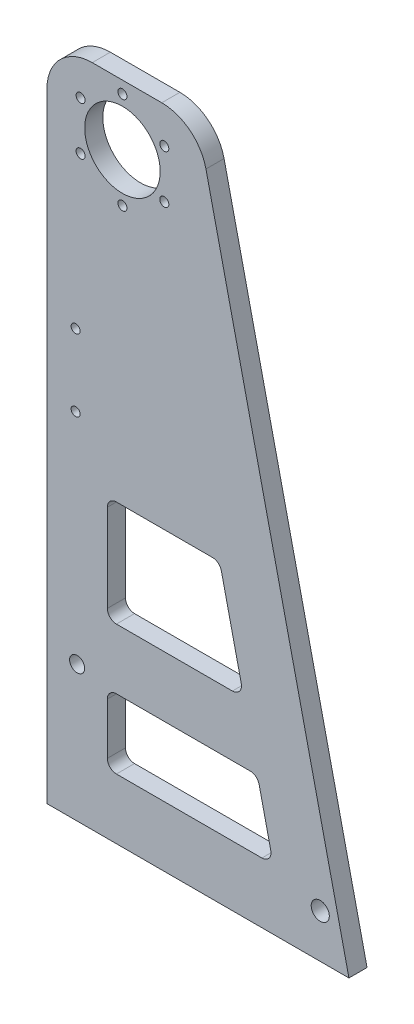
SolidWorks part; units mm, degrees
material "Policarbonato"
ref_plane "Plano frontal" through (0, 0, 0) normal (0, 0, 1) x (1, 0, 0)
ref_plane "Plano superior" through (0, 0, 0) normal (0, 1, 0) x (1, 0, 0)
ref_plane "Plano direito" through (0, 0, 0) normal (1, 0, 0) x (0, 0, -1)
sketch "Esboço1" plane through (0, 0, 0) normal (0, 0, 1) x (1, 0, 0)
  line L0 (0, 0) -> (0, 220)
  line L2 (100, 0) -> (0, 0)
  line L3 (0, 220) -> (50, 220)
  line L4 (50, 220) -> (100, 0)
  line L5 (10, 75.5) -> (10, 15) construction
  line L6 (25, 220) -> (25, 180) construction
  line L7 (10, 15) -> (85.7122, 15) construction
  line L8 (85.7122, 15) -> (71.9622, 75.5) construction
  line L9 (71.9622, 75.5) -> (10, 75.5) construction
  line L10 (20, 95) -> (20, 66)
  line L11 (23, 63) -> (61.4135, 63)
  line L12 (64.3389, 66.6649) -> (57.748, 95.6649)
  line L13 (54.8226, 98) -> (23, 98)
  line L14 (20, 40) -> (20, 23)
  line L15 (23, 20) -> (71.1862, 20)
  line L16 (74.1116, 23.6649) -> (70.248, 40.6649)
  line L17 (23, 43) -> (67.3226, 43)
  circle A0 centre (25, 200) radius 12.5
  circle A1 centre (25, 200) radius 16 construction
  circle A2 centre (25, 216) radius 1.5
  arc A8 (70.248, 40.6649) -> (67.3226, 43) centre (67.3226, 40) ccw
  arc A9 (71.1862, 20) -> (74.1116, 23.6649) centre (71.1862, 23) ccw
  arc A10 (20, 23) -> (23, 20) centre (23, 23) ccw
  arc A11 (20, 40) -> (23, 43) centre (23, 40) cw
  arc A12 (57.748, 95.6649) -> (54.8226, 98) centre (54.8226, 95) ccw
  arc A13 (61.4135, 63) -> (64.3389, 66.6649) centre (61.4135, 66) ccw
  arc A14 (20, 66) -> (23, 63) centre (23, 66) ccw
  arc A15 (20, 95) -> (23, 98) centre (23, 95) cw
  circle A16 centre (38.8564, 208) radius 1.5
  circle A17 centre (38.8564, 192) radius 1.5
  circle A18 centre (25, 184) radius 1.5
  circle A19 centre (11.1436, 192) radius 1.5
  circle A20 centre (11.1436, 208) radius 1.5
  circle A21 centre (10, 45) radius 2.5
  point P26 (22.5, 105)
  point P49 (20, 63)
  point P55 (25, 175)
  point P56 (25, 200)
  dimension "D3" = 20
  dimension "D4" = 25
  dimension "D6" = 32
  dimension "D7" = 3
  dimension "D21" = 3
  dimension "D15" = 10
  dimension "D16" = 45
  dimension "D17" = 5
  dimension "D1" = 220
  dimension "D2" = 100
  dimension "D5" = 50
  dimension "D9" = 25
  dimension "D10" = 6
  dimension "D11" = 20
  dimension "D12" = 20
  dimension "D13" = 15
  dimension "D14" = 20
  dimension "D18" = 10
  dimension "D20" = 20
  dimension "D22" = 23
  dimension "D8" = 35
extrude "Ressalto-extrusão2" add sketch "Esboço1" along normal blind 6
fillet "Filete1" radius 15 2 edges at (0, 220, 3) (50, 220, 3)
sketch "Esboço2" plane through (0, 0, 6) normal (0, 0, 1) x (1, 0, 0)
  circle A1 centre (90.5, 14.5) radius 3
  ellipse E2 centre (9.5, 117.2025) end of major axis (8, 117.2025) minor radius 1.4266
  ellipse E3 centre (9.5, 140.9789) end of major axis (8, 140.9789) minor radius 1.4266
extrude "Corte-extrusão1" cut sketch "Esboço2" against normal through all
